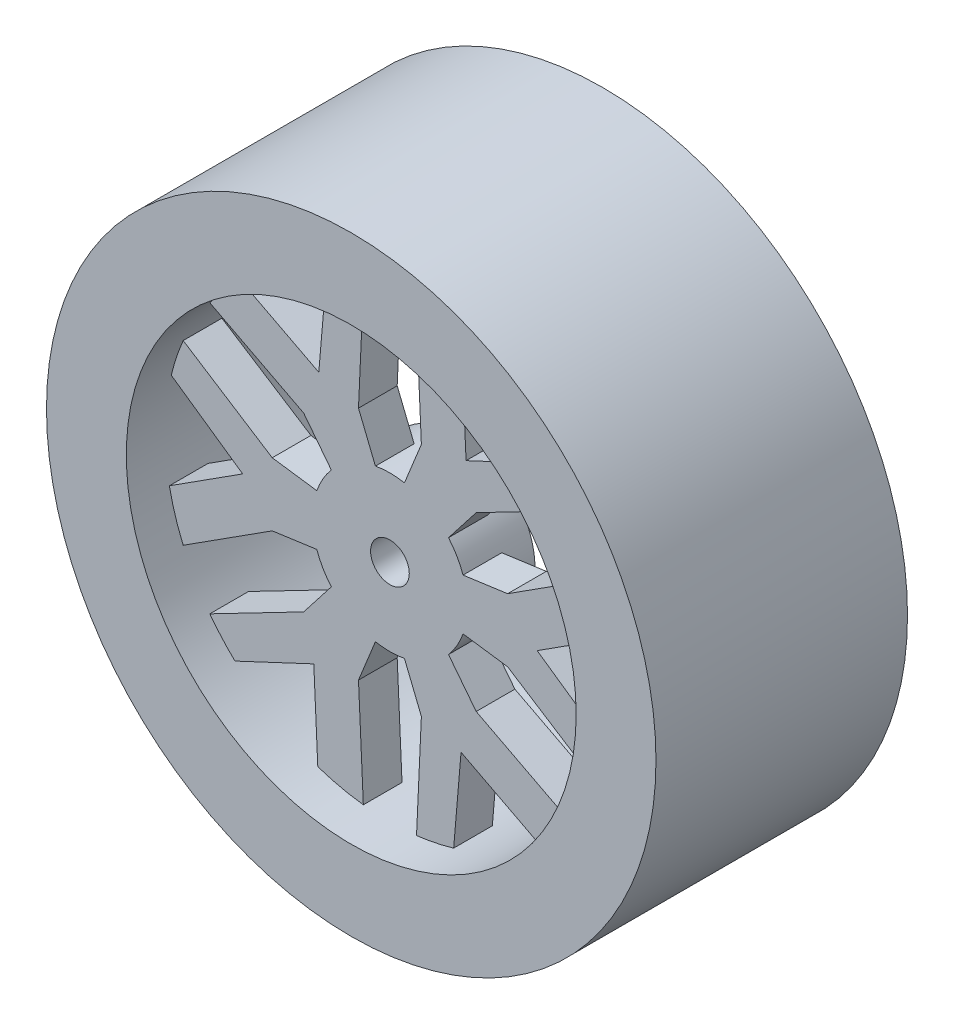
SolidWorks part; units mm, degrees
ref_plane "Plan de face" through (0, 0, 0) normal (0, 0, 1) x (1, 0, 0)
ref_plane "Plan de dessus" through (0, 0, 0) normal (0, 1, 0) x (1, 0, 0)
ref_plane "Plan de droite" through (0, 0, 0) normal (1, 0, 0) x (0, 0, -1)
sketch "Esquisse1" plane through (0, 0, 0) normal (0, 0, 1) x (1, 0, 0)
  circle A0 centre (0, 0) radius 31.5
  dimension "D1" = 63
extrude "Boss.-Extru.1" add sketch "Esquisse1" along normal blind 26
sketch "Esquisse3" plane through (0, 0, 26) normal (0, 0, 1) x (1, 0, 0)
  circle A0 centre (0, 0) radius 23.25
  dimension "D1" = 46.5
extrude "Enlèv. mat.-Extru.2" cut sketch "Esquisse3" against normal blind 4
sketch "Esquisse4" plane through (0, 0, 0) normal (0, 0, -1) x (-1, 0, 0)
  circle A0 centre (0, 0) radius 23.25
  dimension "D1" = 46.5
extrude "Enlèv. mat.-Extru.3" cut sketch "Esquisse4" against normal blind 18
ref_axis "Axe1" through (0, 0, 27.3) along (0, 0, -1)
sketch "Esquisse6" plane through (0, 0, 18) normal (0, 0, -1) x (-1, 0, 0)
  circle A0 centre (0, 0) radius 8
  dimension "D1" = 16
extrude "Boss.-Extru.5" add sketch "Esquisse6" along normal blind 3
sketch "Esquisse2" plane through (0, 0, 26) normal (0, 0, 1) x (1, 0, 0)
  circle A0 centre (0, 0) radius 2
  dimension "D1" = 4
extrude "Enlèv. mat.-Extru.4" cut sketch "Esquisse2" against normal through all
sketch "Esquisse7" plane through (0, 0, 15) normal (0, 0, -1) x (-1, 0, 0)
  line L0 (-3.4641, 6) -> (3.4641, 6)
  line L1 (3.4641, 6) -> (6.9282, 0)
  line L2 (6.9282, 0) -> (3.4641, -6)
  line L3 (3.4641, -6) -> (-3.4641, -6)
  line L4 (-3.4641, -6) -> (-6.9282, 0)
  line L5 (-6.9282, 0) -> (-3.4641, 6)
  point P3 (0, 6)
  dimension "D1" = 12
  dimension "D2" = 12
  dimension "D3" = 12
extrude "Enlèv. mat.-Extru.5" cut sketch "Esquisse7" against normal up to surface (3 mm away) up to face at (-23.25, 0, 18)
sketch "Esquisse8" plane through (0, 0, 22) normal (0, 0, 1) x (1, 0, 0)
  line L0 (-3.25, 12.1718) -> (-1.5, 7.8581)
  line L2 (1.5, 7.8581) -> (3.25, 12.1718)
  line L3 (3.25, 12.1718) -> (2.75, 23.0868)
  line L5 (-2.75, 23.0868) -> (-3.25, 12.1718)
  circle A0 centre (0, 0) radius 23.25 construction
  circle A1 centre (0, 0) radius 23.25 construction
  arc A4 (-2.75, 23.0868) -> (2.75, 23.0868) centre (0, 0) cw
  arc A5 (1.5, 7.8581) -> (-1.5, 7.8581) centre (0, 0) ccw
  dimension "D4" = 8
  dimension "D1" = 5.5
  dimension "D2" = 3
  dimension "D3" = 6.5
extrude "Enlèv. mat.-Extru.8" cut sketch "Esquisse8" against normal through all
pattern_circular "Répétition circulaire1" count 6 over 360 about axis through (0, 0, 27.3) along (0, 0, -1) of "Enlèv. mat.-Extru.8" reverse direction yes
sketch "Esquisse9" plane through (0, 0, 22) normal (0, 0, 1) x (1, 0, 0)
  line L0 (7.869, 13.0311) -> (7.4571, 22.0217)
  line L1 (7.869, 13.0311) -> (16.0174, 16.8524)
  line L2 (3.25, 12.1718) -> (2.75, 23.0868) construction
  arc A0 (16.0174, 16.8524) -> (7.4571, 22.0217) centre (0, 0) ccw
  circle A1 centre (0, 0) radius 23.25 construction
  dimension "D1" = 9
  dimension "D2" = 10
extrude "Enlèv. mat.-Extru.9" cut sketch "Esquisse9" against normal through all
pattern_circular "Répétition circulaire2" count 6 every 60 about axis through (0, 0, 27.3) along (0, 0, -1) of "Enlèv. mat.-Extru.9"
